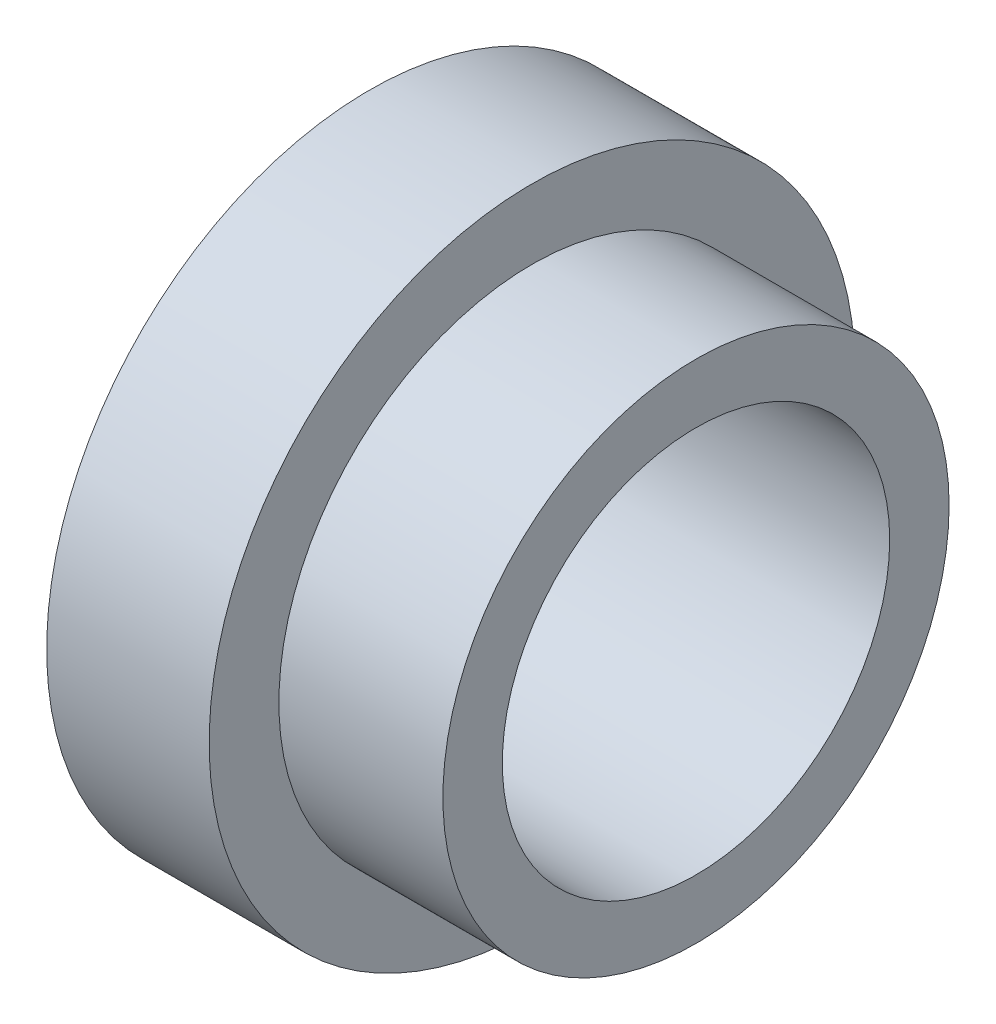
SolidWorks part; units mm, degrees
ref_plane "Front Plane" through (0, 0, 0) normal (0, 0, 1) x (1, 0, 0)
ref_plane "Top Plane" through (0, 0, 0) normal (0, 1, 0) x (1, 0, 0)
ref_plane "Right Plane" through (0, 0, 0) normal (1, 0, 0) x (0, 0, -1)
sketch "Sketch1" plane through (0, 0, 0) normal (1, 0, 0) x (0, 0, -1)
  circle A0 centre (0, 0) radius 12.5
  circle A1 centre (0, 0) radius 7.5
  dimension "D1" = 25
  dimension "D2" = 15
extrude "Boss-Extrude1" add sketch "Sketch1" along normal blind 6.29
sketch "Sketch2" plane through (6.29, 0, 0) normal (1, 0, 0) x (0, 0, -1)
  circle A0 centre (0, 0) radius 9.8
  circle A1 centre (0, 0) radius 7.5
  dimension "D1" = 19.6
extrude "Boss-Extrude2" add sketch "Sketch2" along normal blind 6.35
